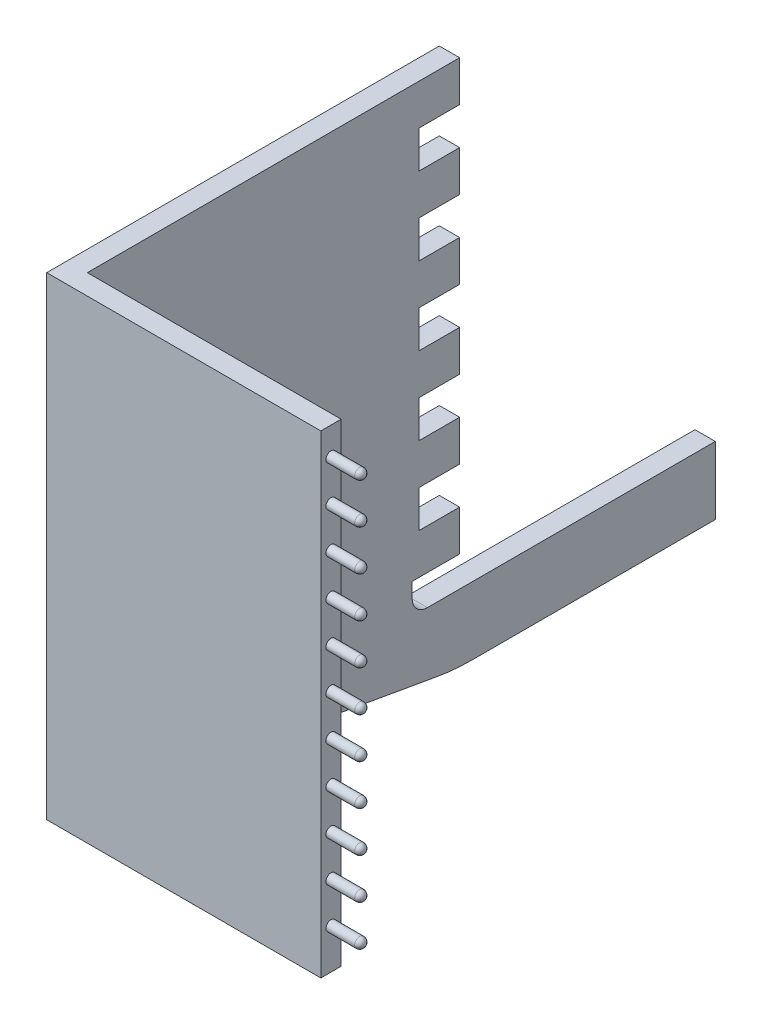
SolidWorks part; units mm, degrees
ref_plane "Alzado" through (0, 0, 0) normal (0, 0, 1) x (1, 0, 0)
ref_plane "Planta" through (0, 0, 0) normal (0, 1, 0) x (1, 0, 0)
ref_plane "Vista lateral" through (0, 0, 0) normal (1, 0, 0) x (0, 0, -1)
sketch "Croquis1" plane through (0, 0, 0) normal (0, 0, 1) x (1, 0, 0)
  line L1 (20.25, 35) -> (-20.25, 35)
  line L2 (20.25, 35) -> (20.25, -35)
  line L3 (20.25, -35) -> (-20.25, -35)
  line L4 (-20.25, 35) -> (-20.25, -35)
  line L5 (20.25, 35) -> (-20.25, -35) construction
  line L6 (20.25, -35) -> (-20.25, 35) construction
  point P0 (0, 0)
  dimension "D1" = 70
  dimension "D2" = 40.5
extrude "Saliente-Extruir1" add sketch "Croquis1" along normal blind 3
sketch "Croquis2" plane through (0, 0, 0) normal (0, 0, -1) x (-1, 0, 0)
  line L0 (20.25, -35) -> (-20.25, -35) construction
  line L1 (20.25, 35) -> (17.25, 35)
  line L2 (20.25, 35) -> (20.25, -35)
  line L3 (20.25, -35) -> (17.25, -35)
  line L4 (17.25, 35) -> (17.25, -35)
  dimension "D1" = 3
extrude "Saliente-Extruir2" add sketch "Croquis2" along normal blind 30
sketch "Croquis3" plane through (20.25, 0, 0) normal (1, 0, 0) x (0, 0, -1)
  line L0 (-1.5, 35) -> (-1.5, -35) construction
  line L1 (-3, 35) -> (0, 35) construction
  line L2 (-3, -35) -> (0, -35) construction
  circle A0 centre (-1.5, 30.9569) radius 0.75
  circle A1 centre (-1.5, 24.9569) radius 0.75
  circle A2 centre (-1.5, 18.9569) radius 0.75
  circle A3 centre (-1.5, 12.9569) radius 0.75
  circle A4 centre (-1.5, 6.9569) radius 0.75
  circle A5 centre (-1.5, 0.9569) radius 0.75
  circle A6 centre (-1.5, -5.0431) radius 0.75
  circle A7 centre (-1.5, -11.0431) radius 0.75
  circle A8 centre (-1.5, -17.0431) radius 0.75
  circle A9 centre (-1.5, -23.0431) radius 0.75
  circle A10 centre (-1.5, -29.0431) radius 0.75
  dimension "D1" = 1.5
  dimension "D2" = 11
extrude "Saliente-Extruir3" add sketch "Croquis3" along normal blind 5
fillet "Redondeo5" radius 0.75 11 edges at (25.25, 31.7069, 1.5) (25.25, -28.2931, 1.5) (25.25, -22.2931, 1.5) (25.25, -16.2931, 1.5) (25.25, -10.2931, 1.5) (25.25, -4.2931, 1.5) (25.25, 1.7069, 1.5) (25.25, 7.7069, 1.5) (25.25, 13.7069, 1.5) (25.25, 19.7069, 1.5) (25.25, 25.7069, 1.5)
sketch "Croquis4" plane through (-17.25, 0, 0) normal (1, 0, 0) x (0, 0, -1)
  line L0 (30, 35) -> (30, -35) construction
  line L1 (30, 35) -> (55, 35)
  line L2 (30, 35) -> (30, -35)
  line L3 (30, -35) -> (55, -35)
  line L4 (55, 35) -> (55, -35)
  line L5 (30, -35) -> (0, -35) construction
  dimension "D1" = 70
  dimension "D2" = 0
  dimension "D3" = 25
extrude "Saliente-Extruir5" add sketch "Croquis4" against normal blind 3
sketch "Croquis5" plane through (0, 0, -55) normal (0, 0, -1) x (-1, 0, 0)
  line L3 (17.25, 29) -> (20.25, 29)
  line L4 (17.25, 35) -> (17.25, -35)
  line L5 (17.25, -35) -> (20.25, -35)
  line L6 (20.25, -35) -> (20.25, 35)
  line L7 (20.25, 35) -> (17.25, 35)
  line L8 (17.25, 35) -> (17.25, -35) construction
  line L9 (17.25, -35) -> (20.25, -35) construction
  line L10 (20.25, -35) -> (20.25, 35) construction
  line L11 (20.25, 35) -> (17.25, 35) construction
  line L12 (20.25, 29) -> (20.25, 23.5)
  line L13 (20.25, 23.5) -> (17.25, 23.5)
  line L14 (17.25, 23.5) -> (17.25, 29)
  line L15 (17.25, 17.5) -> (20.25, 17.5)
  line L16 (20.25, 17.5) -> (20.25, 12)
  line L17 (20.25, 12) -> (17.25, 12)
  line L18 (17.25, 12) -> (17.25, 17.5)
  line L19 (17.25, 6) -> (20.25, 6)
  line L20 (20.25, 6) -> (20.25, 0.5)
  line L21 (20.25, 0.5) -> (17.25, 0.5)
  line L22 (17.25, 0.5) -> (17.25, 6)
  line L23 (17.25, -5.5) -> (20.25, -5.5)
  line L24 (20.25, -5.5) -> (20.25, -11)
  line L25 (20.25, -11) -> (17.25, -11)
  line L26 (17.25, -11) -> (17.25, -5.5)
  line L27 (17.25, -17) -> (20.25, -17)
  line L28 (20.25, -17) -> (20.25, -22.5)
  line L29 (20.25, -22.5) -> (17.25, -22.5)
  line L30 (17.25, -22.5) -> (17.25, -17)
  dimension "D2" = 5.5
  dimension "D3" = 6
  dimension "D1" = 0
  dimension "D4" = 5
extrude "Cortar-Extruir1" cut sketch "Croquis5" against normal blind 6
sketch "Croquis6" plane through (-20.25, 0, 0) normal (-1, 0, 0) x (0, 0, 1)
  line L2 (-48, 35.7325) -> (-48, -30.7325)
  line L3 (-50.25, -32.9825) -> (-92.775, -32.9825)
  arc A1 (-50.25, -32.9825) -> (-48, -30.7325) centre (-50.25, -30.7325) ccw
sketch "Croquis7" plane through (-20.25, 0, 0) normal (-1, 0, 0) x (0, 0, 1)
  line L0 (3, 35) -> (3, -35) construction
  line L1 (3, 35) -> (3, -35) construction
  line L2 (3, -35) -> (-55, -35) construction
  line L3 (3, -35) -> (-55, -35) construction
  line L4 (-9, -35) -> (-51.6862, -42.5267)
  line L5 (-50.25, -32.9825) -> (-92.775, -32.9825) construction
  line L6 (-50.25, -32.9825) -> (-92.775, -32.9825)
  line L7 (-92.775, -32.9825) -> (-92.775, -42.9825)
  line L8 (-92.775, -42.9825) -> (-56.8957, -42.9825)
  line L9 (-50.25, -32.9825) -> (-9, -35)
  arc A0 (-51.6862, -42.5267) -> (-56.8957, -42.9825) centre (-56.8957, -12.9825) cw
  dimension "D4" = 30
  dimension "D1" = 12
  dimension "D2" = 10
  dimension "D3" = 10
extrude "Saliente-Extruir6" add sketch "Croquis7" against normal blind 3
sketch "Croquis8" plane through (-20.25, 0, 0) normal (-1, 0, 0) x (0, 0, 1)
  line L0 (-48, 35.7325) -> (-48, -30.7325) construction
  line L1 (-50.25, -32.9825) -> (-92.775, -32.9825) construction
  line L2 (-48, -28.5) -> (-48, -30.7325)
  line L3 (-50.25, -32.9825) -> (-92.775, -32.9825)
  line L4 (-49, -22.5) -> (-55, -22.5) construction
  line L5 (-49, -22.5) -> (-55, -22.5) construction
  line L6 (-48, -28.5) -> (-92.775, -28.5)
  line L7 (-92.775, -28.5) -> (-92.775, -32.9825)
  arc A0 (-50.25, -32.9825) -> (-48, -30.7325) centre (-50.25, -30.7325) ccw construction
  arc A1 (-50.25, -32.9825) -> (-48, -30.7325) centre (-50.25, -30.7325) ccw
  dimension "D1" = 6
extrude "Cortar-Extruir2" cut sketch "Croquis8" against normal through all both and the other way through all
